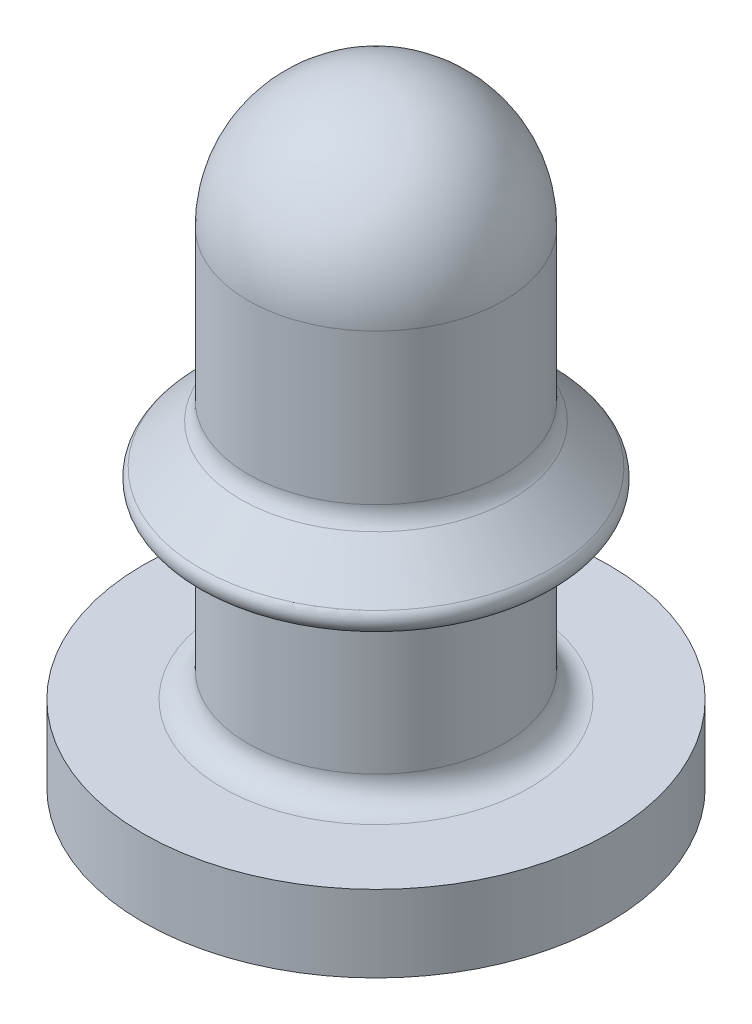
SolidWorks part; units mm, degrees
ref_plane "Front Plane" through (0, 0, 0) normal (0, 0, 1) x (1, 0, 0)
ref_plane "Top Plane" through (0, 0, 0) normal (0, 1, 0) x (1, 0, 0)
ref_plane "Right Plane" through (0, 0, 0) normal (1, 0, 0) x (0, 0, -1)
sketch "Sketch1" plane through (0, 0, 0) normal (0, 1, 0) x (1, 0, 0)
  circle A0 centre (0, 0) radius 2.5
  dimension "D1" = 5
extrude "Boss-Extrude1" add sketch "Sketch1" along normal blind 12
sketch "Sketch6" plane through (0, 0, 0) normal (0, -1, 0) x (1, 0, 0)
  circle A0 centre (0, 0) radius 4.55
  dimension "D1" = 9.1
extrude "Boss-Extrude3" add sketch "Sketch6" against normal blind 1.5
sketch "Sketch8" plane through (0, 0, 0) normal (0, 0, 1) x (1, 0, 0)
  line L0 (2.5, 6.3536) -> (3.4268, 5.4268)
  line L1 (2.5, 1.5) -> (2.5, 12) construction
  line L2 (3.25, 5) -> (2.5, 5)
  line L3 (2.5, 5) -> (2.5, 6.3536)
  line L5 (4.55, 1.5) -> (-4.55, 1.5) construction
  line L6 (0, 0) -> (0, 12) construction
  line L7 (-4.55, 0) -> (4.55, 0) construction
  line L8 (2.5, 12) -> (-2.5, 12) construction
  arc A0 (3.25, 5) -> (3.4268, 5.4268) centre (3.25, 5.25) ccw
  dimension "D3" = 0.5
  dimension "D4" = 1
  dimension "D1" = 3.5
  dimension "D2" = 45
revolve "Revolve1" add sketch "Sketch8" angle 360 about L6
sketch "Sketch2" plane through (0, 0, 0) normal (0, -1, 0) x (1, 0, 0)
  circle A0 centre (0, 0) radius 1
  dimension "D1" = 2
extrude "Cut-Extrude1" cut sketch "Sketch2" against normal blind 10
draft "Draft1" type of draft neutral plane draft angle 1 faces to draft 1 face at (0, 10, -1) neutral plane through (0, 10, 0) neutral plane normal (0, -1, 0) parameters "D1"=1
sketch "Sketch7" plane through (0, 0, 0) normal (0, 0, 1) x (1, 0, 0)
  line L0 (2.5, 6.3536) -> (2.5, 12) construction
  line L1 (2.5, 12) -> (-2.5, 12) construction
  line L4 (0, 9.5) -> (0, 12) construction
  line L5 (2.5, 9.5) -> (3.0807, 9.5)
  line L6 (3.0807, 9.5) -> (3.0807, 12.5807)
  line L7 (3.0807, 12.5807) -> (0, 12.5807)
  line L8 (0, 12.5807) -> (0, 12)
  arc A0 (2.5, 9.5) -> (0, 12) centre (0, 9.5) ccw
  dimension "D1" = 3.0807
revolve "Cut-Revolve3" cut sketch "Sketch7" angle 360 about L4
sketch "Sketch3" plane through (0, 10, 0) normal (0, -1, 0) x (1, 0, 0)
  line L0 (1.151, 0.2338) -> (0.746, 0)
  line L1 (0.746, 0) -> (1.151, -0.2338)
  line L2 (0, 0) -> (1.1746, 0) construction
  line L3 (1.151, 0.2338) -> (1.151, -0.2338) construction
  line L6 (-0.373, -1.1138) -> (-0.373, -0.6461)
  line L7 (-0.373, -0.6461) -> (-0.778, -0.8799)
  line L10 (-0.373, -1.1138) -> (-0.778, -0.8799) construction
  line L11 (-0.778, 0.8799) -> (-0.373, 0.6461)
  line L14 (-0.373, 0.6461) -> (-0.373, 1.1138)
  line L15 (-0.778, 0.8799) -> (-0.373, 1.1138) construction
  arc A1 (-0.778, -0.8799) -> (-0.373, -1.1138) centre (0, 0) ccw
  arc A2 (-0.373, 1.1138) -> (-0.778, 0.8799) centre (0, 0) ccw
  circle A7 centre (0, 0) radius 1.1746 construction
  arc A8 (1.151, -0.2338) -> (1.151, 0.2338) centre (0, 0) ccw
  circle A9 centre (0, 0) radius 1 construction
  point P16 (0, 0)
  dimension "D1" = 0.254
extrude "Boss-Extrude2" add sketch "Sketch3" along normal up to surface (10 mm away) up to face at (0, 0, 1.1746)
sketch "ref_for_revolve" plane through (0, 0, 0) normal (0, -1, 0) x (1, 0, 0)
  circle A0 centre (0, 0) radius 1.1746 construction
sketch "Sketch4" plane through (0, 0, 0) normal (0, 0, 1) x (1, 0, 0)
  line L1 (1.1746, 0) -> (0.746, 0.5107)
  line L2 (0.746, 0.5107) -> (0, 0.5107)
  line L4 (0, 0.5107) -> (0, 0)
  line L5 (0.746, 0.5107) -> (0.746, 0) construction
  line L6 (0.746, 0) -> (1.1746, 0) construction
  line L7 (1.1746, 0) -> (0, 0)
  line L8 (-0.373, 0) -> (1.151, 0) construction
  line L9 (-1.1746, 0) -> (1.1746, 0) construction
  dimension "D1" = 50
revolve "Cut-Revolve1" cut sketch "Sketch4" angle 360 about L4
fillet "Fillet1" radius 0.5 3 edges at (0, 1.5, -2.5) (0, 5, -2.5) (0, 6.3536, -2.5)
